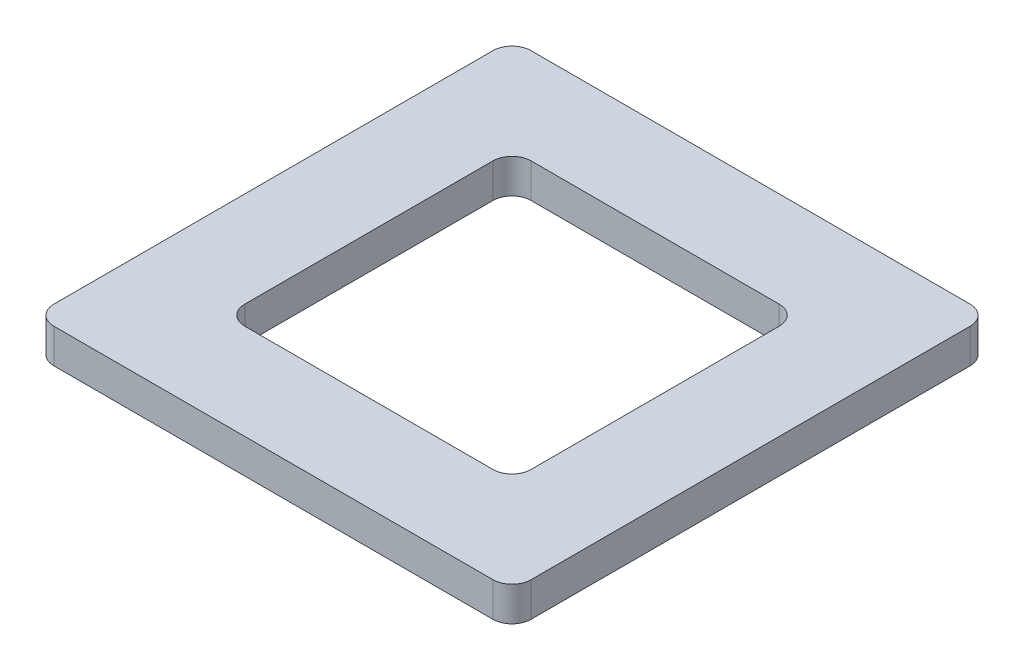
SolidWorks part; units mm, degrees
ref_plane "前视基准面" through (0, 0, 0) normal (0, 0, 1) x (1, 0, 0)
ref_plane "上视基准面" through (0, 0, 0) normal (0, 1, 0) x (1, 0, 0)
ref_plane "右视基准面" through (0, 0, 0) normal (1, 0, 0) x (0, 0, -1)
other "Configuration Table"
sketch "草图1" plane through (0, 0, 0) normal (0, 1, 0) x (1, 0, 0)
  line L1 (-125, -125) -> (125, -125)
  line L2 (-125, -125) -> (-125, 125)
  line L3 (-125, 125) -> (125, 125)
  line L4 (125, -125) -> (125, 125)
  line L5 (-75, 75) -> (75, 75)
  line L6 (-75, 75) -> (-75, -75)
  line L7 (-75, -75) -> (75, -75)
  line L8 (75, 75) -> (75, -75)
  point P4 (-125, 0)
  point P6 (0, 125)
  point P11 (0, 75)
  point P12 (-75, 0)
  dimension "D3" = 150
  dimension "D4" = 150
  dimension "D1" = 250
  dimension "D2" = 250
extrude "凸台-拉伸1" add sketch "草图1" along normal blind 18
fillet "圆角1" radius 10 4 edges at (-125, 9, -125) (125, 9, -125) (125, 9, 125) (-125, 9, 125)
fillet "圆角2" radius 10 4 edges at (75, 9, 75) (-75, 9, 75) (75, 9, -75) (-75, 9, -75)
